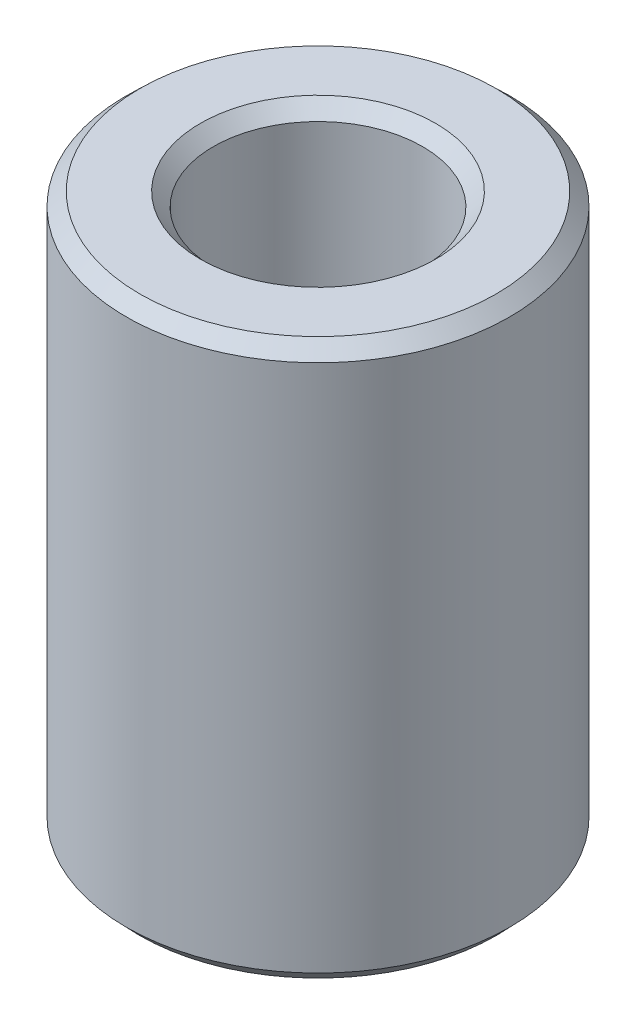
SolidWorks part; units mm, degrees
ref_plane "Front Plane" through (0, 0, 0) normal (0, 0, 1) x (1, 0, 0)
ref_plane "Top Plane" through (0, 0, 0) normal (0, 1, 0) x (1, 0, 0)
ref_plane "Right Plane" through (0, 0, 0) normal (1, 0, 0) x (0, 0, -1)
sketch "Sketch1" plane through (0, 0, 0) normal (0, 1, 0) x (1, 0, 0)
  circle A0 centre (0, 0) radius 10
  dimension "SLEEVE_OD" = 20
extrude "Boss-Extrude1" add sketch "Sketch1" along normal blind 28.9695
sketch "Sketch2" plane through (0, 0, 0) normal (0, 1, 0) x (1, 0, 0)
  circle A0 centre (0, 0) radius 5.4593
  dimension "BORE_D" = 10.9187
extrude "Cut-Extrude1" cut sketch "Sketch2" along normal through all
chamfer "Chamfer1" distance 0.6811 angle 46.134 4 edges at (0, 28.9695, 5.4593) (0, 0, 5.4593) (0, 0, 10) (0, 28.9695, 10) first distance on face at (0, 28.9695, 5.4593) first distance on face at (0, 0, 5.4593) first distance on face at (0, 28.9695, 10)
